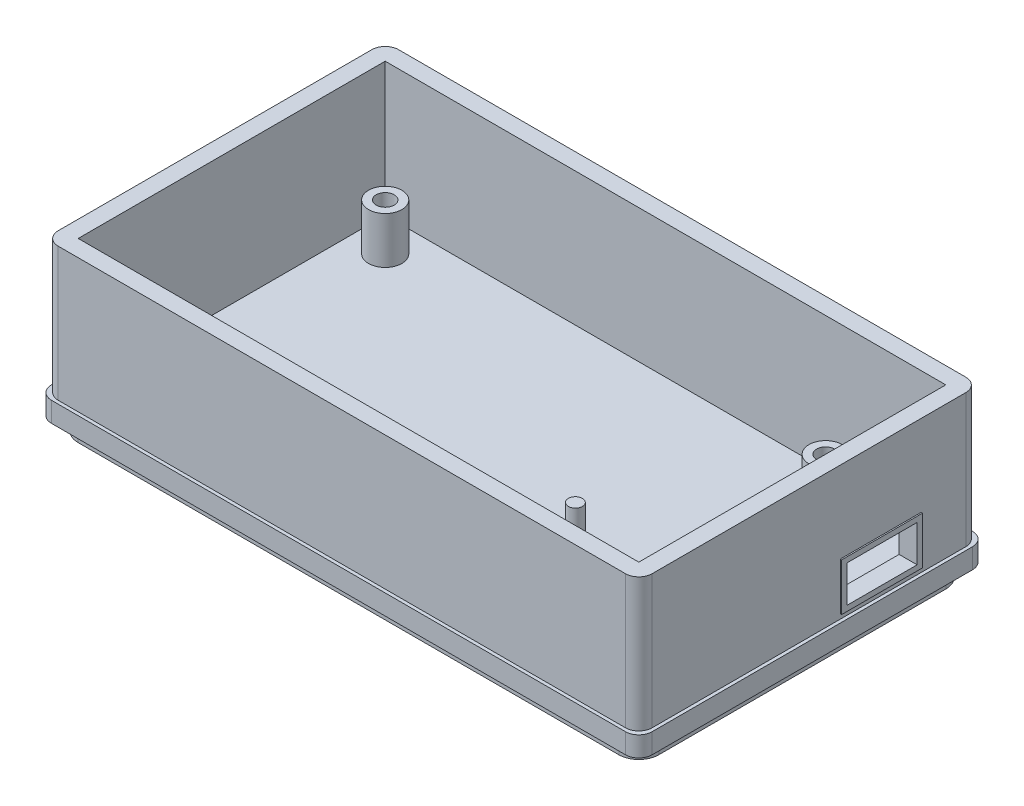
SolidWorks part; units mm, degrees
ref_plane "Front Plane" through (0, 0, 0) normal (0, 0, 1) x (1, 0, 0)
ref_plane "Top Plane" through (0, 0, 0) normal (0, 1, 0) x (1, 0, 0)
ref_plane "Right Plane" through (0, 0, 0) normal (1, 0, 0) x (0, 0, -1)
sketch "Sketch1" plane through (0, 0, 0) normal (0, 1, 0) x (1, 0, 0)
  line L1 (-45, 26) -> (45, 26)
  line L2 (-45, 26) -> (-45, -26)
  line L3 (-45, -26) -> (45, -26)
  line L4 (45, 26) -> (45, -26)
  dimension "D1" = 52
  dimension "D2" = 90
  dimension "D3" = 45
  dimension "D4" = 26
extrude "Boss-Extrude1" add sketch "Sketch1" along normal blind 3
sketch "Sketch3" plane through (0, 0, 0) normal (0, 1, 0) x (1, 0, 0)
  line L1 (-41.5, 22.5) -> (41.5, 22.5)
  line L2 (-41.5, 22.5) -> (-41.5, -22.5)
  line L3 (-41.5, -22.5) -> (41.5, -22.5)
  line L4 (41.5, 22.5) -> (41.5, -22.5)
  dimension "D1" = 45
  dimension "D2" = 83
  dimension "D3" = 41.5
  dimension "D4" = 22.5
sketch "Sketch4" plane through (0, 0, 0) normal (0, 1, 0) x (1, 0, 0)
  line L0 (-41.5, 22.5) -> (41.5, 22.5) construction
  line L1 (41.5, 22.5) -> (41.5, -22.5) construction
  line L2 (-41.5, -22.5) -> (41.5, -22.5) construction
  line L3 (-41.5, 22.5) -> (-41.5, -22.5) construction
  circle A0 centre (29, 18) radius 2.5
  circle A1 centre (29, -19.5) radius 2.5
  circle A2 centre (-37, 18) radius 2.5
  circle A3 centre (-37, -16.5) radius 2.5
  dimension "D2" = 5
  dimension "D4" = 5
  dimension "D1" = 4.5
  dimension "D3" = 12.5
  dimension "D5" = 3
  dimension "D8" = 4.5
  dimension "D9" = 6
extrude "Boss-Extrude2" add sketch "Sketch4" along normal blind 7 from surface starting at face at (0, 3, 0)
sketch "Sketch5" plane through (0, 0, 0) normal (0, 1, 0) x (1, 0, 0)
  circle A0 centre (-37, 18) radius 1.35
  circle A1 centre (-37, -16.5) radius 1.35
  circle A3 centre (29, 18) radius 1.35
  dimension "D1" = 2.7
extrude "Cut-Extrude2" cut sketch "Sketch5" against normal through all both and the other way through all from surface starting at face at (-37, 10, -15.5)
sketch "Sketch6" plane through (0, 0, 0) normal (0, 1, 0) x (1, 0, 0)
  circle A0 centre (29, -19.5) radius 1.05
  dimension "D1" = 2.1
extrude "Boss-Extrude3" add sketch "Sketch6" along normal blind 12.5 from surface starting at face at (29, 10, 22)
sketch "Sketch7" plane through (0, 0, 0) normal (0, 1, 0) x (1, 0, 0)
  line L4 (40.5, 21.5) -> (-40.5, 21.5)
  line L5 (-40.5, 21.5) -> (-40.5, -21.5)
  line L6 (-40.5, -21.5) -> (40.5, -21.5)
  line L7 (40.5, -21.5) -> (40.5, 21.5)
  line L8 (43.5, 24.5) -> (-43.5, 24.5)
  line L9 (43.5, -24.5) -> (43.5, 24.5)
  line L10 (-43.5, -24.5) -> (43.5, -24.5)
  line L11 (-43.5, 24.5) -> (-43.5, -24.5)
  line L12 (43.5, 24.5) -> (-43.5, 24.5)
  line L13 (43.5, -24.5) -> (43.5, 24.5)
  line L14 (-43.5, -24.5) -> (43.5, -24.5)
  line L15 (-43.5, 24.5) -> (-43.5, -24.5)
  dimension "D1" = 2
  dimension "D2" = 3
extrude "Boss-Extrude4" add sketch "Sketch7" against normal blind 2
fillet "Fillet1" radius 3 4 edges at (-43.5, -1, 24.5) (-43.5, -1, -24.5) (43.5, -1, 24.5) (43.5, -1, -24.5)
sketch "Sketch8" plane through (0, 0, 0) normal (0, 1, 0) x (1, 0, 0)
  line L4 (44.5, 25.5) -> (-44.5, 25.5)
  line L5 (-44.5, 25.5) -> (-44.5, -25.5)
  line L6 (-44.5, -25.5) -> (44.5, -25.5)
  line L7 (44.5, -25.5) -> (44.5, 25.5)
  line L8 (42, 23) -> (-42, 23)
  line L9 (42, -23) -> (42, 23)
  line L10 (-42, -23) -> (42, -23)
  line L11 (-42, 23) -> (-42, -23)
  line L12 (42, 23) -> (-42, 23)
  line L13 (42, -23) -> (42, 23)
  line L14 (-42, -23) -> (42, -23)
  line L15 (-42, 23) -> (-42, -23)
  dimension "D1" = 0.5
  dimension "D2" = 2.5
extrude "Boss-Extrude8" add sketch "Sketch8" along normal blind 20 from surface starting at face at (29, 3, 22)
fillet "Fillet2" radius 2 8 edges at (-45, 1.5, 26) (-44.5, 13, 25.5) (-45, 1.5, -26) (-44.5, 13, -25.5) (45, 1.5, -26) (45, 1.5, 26) (44.5, 13, -25.5) (44.5, 13, 25.5)
sketch "Sketch9" plane through (0, 0, 0) normal (1, 0, 0) x (0, 0, -1)
  line L0 (23.5, 3) -> (-23.5, 3) construction
  line L1 (5.5, 10) -> (16, 10)
  line L2 (5.5, 10) -> (5.5, 4.5)
  line L3 (5.5, 4.5) -> (16, 4.5)
  line L4 (16, 10) -> (16, 4.5)
  dimension "D1" = 10.5
  dimension "D2" = 5.5
  dimension "D3" = 1.5
  dimension "D4" = 7.5
extrude "Cut-Extrude3" cut sketch "Sketch9" along normal blind 15 from surface starting at face at (42, 13, 0)
sketch "Sketch10" plane through (0, 0, 0) normal (1, 0, 0) x (0, 0, -1)
  line L10 (16, 10) -> (5.5, 10)
  line L11 (5.5, 10) -> (5.5, 4.5)
  line L12 (5.5, 4.5) -> (16, 4.5)
  line L13 (16, 4.5) -> (16, 10)
  line L14 (4.7, 10.8) -> (4.7, 3.7)
  line L15 (4.7, 3.7) -> (16.8, 3.7)
  line L16 (16.8, 3.7) -> (16.8, 10.8)
  line L17 (16.8, 10.8) -> (4.7, 10.8)
  line L18 (4.7, 10.8) -> (4.7, 3.7)
  line L19 (4.7, 3.7) -> (16.8, 3.7)
  line L20 (16.8, 3.7) -> (16.8, 10.8)
  line L21 (16.8, 10.8) -> (4.7, 10.8)
  dimension "D1" = 0.8
  dimension "D2" = 0.8
extrude "Boss-Extrude9" add sketch "Sketch10" along normal blind 0.2 from surface starting at face at (44.5, 7.25, -10.75)
